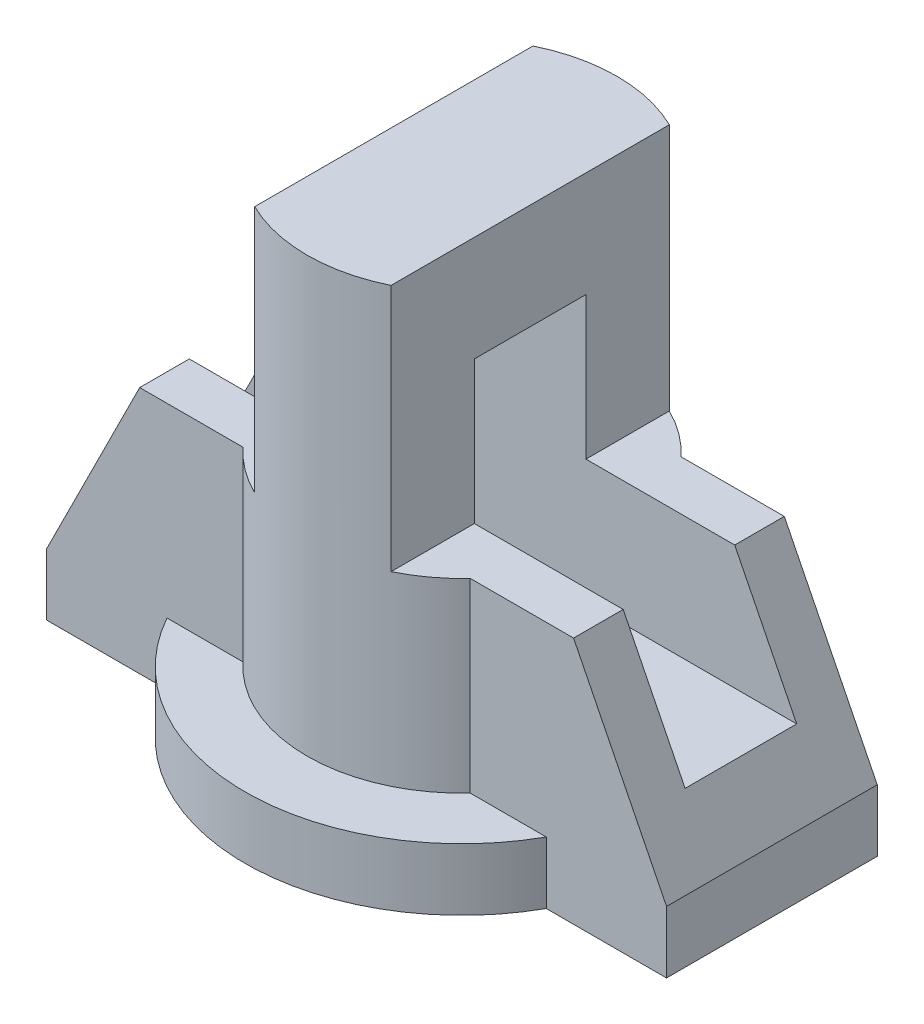
SolidWorks part; units mm, degrees
ref_plane "Front Plane" through (0, 0, 0) normal (0, 0, 1) x (1, 0, 0)
ref_plane "Top Plane" through (0, 0, 0) normal (0, 1, 0) x (1, 0, 0)
ref_plane "Right Plane" through (0, 0, 0) normal (1, 0, 0) x (0, 0, -1)
sketch "Sketch1" plane through (0, 0, 0) normal (0, 1, 0) x (1, 0, 0)
  line L0 (0, 0) -> (-30971.7935, 0) construction
  line L1 (0, 0) -> (0, -30971.7935) construction
  line L2 (11, 22.4499) -> (11, -22.4499)
  line L3 (-11, 22.4499) -> (-11, -22.4499)
  line L4 (-50, 9) -> (-11, 9)
  line L5 (-50, -9) -> (-11, -9)
  line L6 (-50, 17) -> (-11, 17)
  line L7 (-50, -17) -> (-11, -17)
  line L8 (11, 9) -> (50, 9)
  line L9 (11, 17) -> (50, 17)
  line L10 (11, -17) -> (50, -17)
  line L11 (11, -9) -> (50, -9)
  line L12 (-35, 17) -> (-35, 9)
  line L13 (35, 17) -> (35, 9)
  line L14 (35, -17) -> (35, -9)
  line L15 (-35, -17) -> (-35, -9)
  line L16 (-50, 17) -> (-50, 9)
  line L17 (50, 17) -> (50, 9)
  line L18 (50, -17) -> (50, -9)
  line L19 (-50, -17) -> (-50, -9)
  line L20 (-50, 9) -> (-50, -9)
  line L21 (50, 9) -> (50, -9)
  arc A2 (-18.3303, -17) -> (18.3303, -17) centre (0, 0) ccw
  arc A3 (18.3303, 17) -> (-18.3303, 17) centre (0, 0) ccw
  arc A4 (-30.5941, -17) -> (30.5941, -17) centre (0, 0) ccw
  arc A5 (30.5941, 17) -> (-30.5941, 17) centre (0, 0) ccw
  dimension "D1" = 50
  dimension "D8" = 70
  dimension "D2" = 22
  dimension "D3" = 18
  dimension "D4" = 8
  dimension "D5" = 100
  dimension "D6" = 50
  dimension "D7" = 35
extrude "Boss-Extrude2" add sketch "Sketch1" along normal blind 80 contours L2 A3 L3 A2 region at (0, 0, 0)
extrude "Boss-Extrude3" add sketch "Sketch1<6>" along normal blind 10 contours L9 A5 L6 A3 | L7 A4 L10 A2 region at (0, 0, -25.8336) region at (0, 0, 25.8336)
sketch "Sketch1<6>" plane through (0, 0, 0) normal (0, 1, 0) x (1, 0, 0) same geometry as "Sketch1"
extrude "Boss-Extrude4" add sketch "Sketch1<9>" along normal blind 40 contours L6 L16 L4 L12 | L6 L12 L4 L3 | L4 L20 L5 L3 | L19 L7 L15 L5 | L15 L7 L3 L5 | L10 L18 L11 L14 | L10 L14 L11 L2 | L21 L8 L2 L11 | L13 L9 L2 L8 | L17 L9 L13 L8 | L9 A3 L2 | L3 A3 L6 | L7 A2 L3 | L2 A2 L10 region at (13.594, 0, -18.9354) region at (23, 0, -13) region at (-13.594, 0, -18.9354) region at (30.5, 0, 0) region at (-23, 0, -13) region at (23, 0, 13) region at (42.5, 0, -13) region at (-30.5, 0, 0) region at (13.594, 0, 18.9354) region at (42.5, 0, 13) region at (-42.5, 0, -13) region at (-23, 0, 13) region at (-13.594, 0, 18.9354) region at (-42.5, 0, 13)
sketch "Sketch1<9>" plane through (0, 0, 0) normal (0, 1, 0) x (1, 0, 0) same geometry as "Sketch1"
sketch "Sketch2" plane through (0, 0, 17) normal (0, 0, 1) x (1, 0, 0)
  line L0 (-50, 10) -> (-35, 40)
  line L1 (-50, 40) -> (-50, 0) construction
  line L2 (-50, 40) -> (-18.3303, 40) construction
  line L3 (0, 0) -> (0, -50000) construction
  line L4 (50, 10) -> (35, 40)
  line L5 (-50, 0) -> (-30.5941, 0) construction
  line L6 (-50, 10) -> (-50, 40)
  line L7 (-50, 40) -> (-35, 40)
  line L8 (35, 40) -> (50, 40)
  line L9 (50, 40) -> (50, 10)
  dimension "D1" = 70
  dimension "D2" = 10
extrude "Cut-Extrude1" cut sketch "Sketch2" against normal through all
sketch "Sketch3" plane through (-50, 0, 0) normal (-1, 0, 0) x (0, 0, 1)
  line L0 (0, 0) -> (0, -50000) construction
  line L1 (0, 0) -> (-50000, 0) construction
  line L3 (-9, 63) -> (9, 63)
  line L4 (9, 63) -> (9, 20)
  line L5 (9, 20) -> (-9, 20)
  line L6 (-9, 20) -> (-9, 63)
  line L7 (-22.4499, 80) -> (22.4499, 80) construction
  point P8 (0, 63)
  dimension "D1" = 18
  dimension "D2" = 43
  dimension "D3" = 17
extrude "Cut-Extrude2" cut sketch "Sketch3" against normal through all
